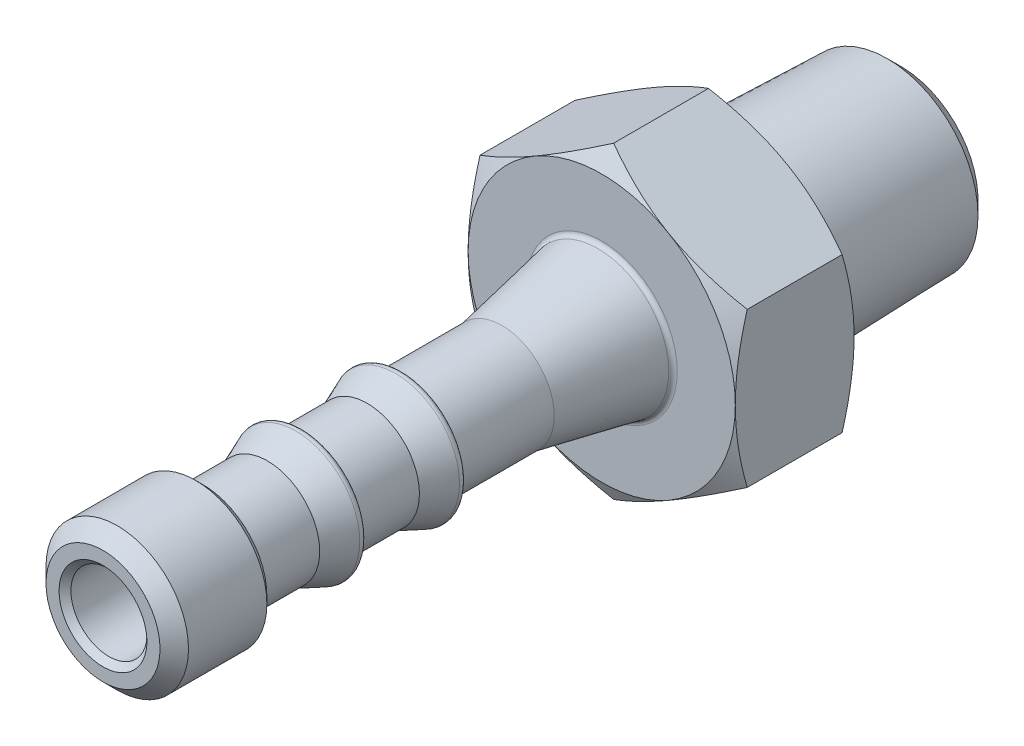
SolidWorks part; units mm, degrees
material "Alloy Steel"
ref_plane "Front Plane" through (0, 0, 0) normal (0, 0, 1) x (1, 0, 0)
ref_plane "Top Plane" through (0, 0, 0) normal (0, 1, 0) x (1, 0, 0)
ref_plane "Right Plane" through (0, 0, 0) normal (1, 0, 0) x (0, 0, -1)
sketch "Sketch1" plane through (0, 0, 0) normal (1, 0, 0) x (0, 0, -1)
  line L0 (-26.67, 0) -> (0, 0) construction
  line L1 (0, 0) -> (6.35, 0) construction
  line L2 (6.35, 0) -> (16.002, 0) construction
  line L3 (-26.67, 3.175) -> (-26.67, -3.175) construction
  line L5 (0, 7.1437) -> (0, -7.1437) construction
  line L6 (-26.67, 2.032) -> (-26.67, -2.032) construction
  line L7 (-26.67, 3.81) -> (-26.67, -3.81) construction
  line L8 (6.35, 7.1437) -> (6.35, -7.1437) construction
  line L9 (16.002, 3.175) -> (16.002, -3.175) construction
  line L10 (6.035, -5.1435) -> (6.035, 5.1435) construction
  line L11 (6.035, 5.1435) -> (16.002, 4.8332) construction
  line L12 (16.002, 4.8332) -> (16.002, -4.8332) construction
  line L13 (6.035, 5.1435) -> (6.9758, 5.1435) construction
  point P26 (6.035, 0)
sketch "Sketch2" plane through (0, 0, 0) normal (1, 0, 0) x (0, 0, -1)
  line L1 (-21.082, 2.794) -> (-17.8771, 2.794)
  line L2 (0, 4.0402) -> (0, 0)
  line L3 (0, 7.1437) -> (0, -7.1437) construction
  line L4 (-26.67, 0) -> (0, 0)
  line L7 (-26.67, 0) -> (-26.67, 3.81)
  line L9 (-26.67, 0) -> (0, 0) construction
  line L14 (-21.336, 3.048) -> (-21.336, 3.81)
  line L15 (-21.336, 3.81) -> (-26.67, 3.81)
  line L18 (-26.67, 7.1437) -> (-21.336, 7.1437) construction
  line L19 (-21.336, 7.1437) -> (-16.002, 7.1437) construction
  line L20 (-16.002, 7.1437) -> (-10.668, 7.1437) construction
  line L21 (-10.668, 7.1437) -> (-5.334, 7.1437) construction
  line L22 (-5.334, 7.1437) -> (0, 7.1437) construction
  line L23 (-26.67, 0) -> (-26.67, 7.1437) construction
  line L24 (-17.8771, 2.794) -> (-16.3512, 3.4105)
  line L25 (-16.002, 3.175) -> (-16.002, 3.048)
  line L26 (-15.748, 2.794) -> (-12.5431, 2.794)
  line L27 (-12.5431, 2.794) -> (-11.0172, 3.4105)
  line L28 (-10.668, 3.175) -> (-10.668, 3.048)
  line L29 (-10.414, 2.794) -> (-5.334, 2.794)
  line L30 (-5.334, 2.794) -> (-0.2055, 3.7909)
  line L38 (-16.256, 3.429) -> (-10.922, 3.429) construction
  arc A0 (-16.3512, 3.4105) -> (-16.002, 3.175) centre (-16.256, 3.175) cw
  arc A1 (-16.002, 3.048) -> (-15.748, 2.794) centre (-15.748, 3.048) ccw
  arc A2 (-11.0172, 3.4105) -> (-10.668, 3.175) centre (-10.922, 3.175) cw
  arc A3 (-10.668, 3.048) -> (-10.414, 2.794) centre (-10.414, 3.048) ccw
  arc A8 (-21.336, 3.048) -> (-21.082, 2.794) centre (-21.082, 3.048) ccw
  arc A10 (-0.2055, 3.7909) -> (0, 4.0402) centre (-0.254, 4.0402) ccw
  point P39 (-16.002, 2.794)
  point P44 (-10.668, 2.794)
  point P66 (-21.336, 2.794)
  dimension "D2" = 0.254
  dimension "D5" = 0.254
  dimension "D6" = 0.254
  dimension "D1" = 22
  dimension "D3" = 1.016
  dimension "D4" = 11
  dimension "D7" = 0.635
revolve "Revolve1" add sketch "Sketch2" angle 360 about L9
chamfer "Chamfer1" distance 0.381 angle 45 1 edges at (3.81, 0, 21.336)
chamfer "Chamfer2" distance 0.762 angle 45 1 edges at (3.81, 0, 26.67)
ref_plane "Plane1" through (0, 0, -16.002) normal (0, 0, 1) x (1, 0, 0)
sketch "Sketch3" plane through (0, 0, -16.002) normal (0, 0, 1) x (1, 0, 0)
  circle A0 centre (0, 0) radius 4.8332
extrude "Boss-Extrude1" add sketch "Sketch3" along normal up to vertex (9.652 mm away) draft 1.783 separate body up to point (0, 0, -6.35) draft outward yes
sketch "Sketch4" plane through (0, 0, -16.002) normal (0, 0, -1) x (-1, 0, 0)
  circle A1 centre (0, 0) radius 4.8332
  circle A2 centre (0, 0) radius 4.8332
  point P0 (0, 4.8332)
  dimension "D1" = 0
curve "Helix/Spiral1" [suppressed]
sketch "Sketch5" plane through (0, 0, 0) normal (1, 0, 0) x (0, 0, -1)
  line L0 (15.9432, 4.935) -> (16.8839, 4.935) construction
  line L1 (16.8839, 4.935) -> (16.4136, 4.1203) construction
  line L2 (16.4136, 4.1203) -> (15.9432, 4.935) construction
  line L3 (16.3548, 4.2221) -> (16.4724, 4.2221) construction
  line L4 (16.002, 4.8332) -> (16.8251, 4.8332) construction
  line L5 (16.4136, 4.1203) -> (16.4136, 4.2221) construction
  line L6 (16.4136, 4.8332) -> (16.4136, 4.935) construction
  line L7 (16.4136, 4.8841) -> (16.8545, 4.8841) construction
  line L8 (16.8545, 4.8841) -> (15.9432, 4.935)
  line L9 (15.9432, 4.935) -> (16.3548, 4.2221)
  line L10 (16.3548, 4.2221) -> (16.4724, 4.2221)
  line L11 (16.4724, 4.2221) -> (16.8545, 4.8841)
  line L12 (16.4136, 4.1203) -> (16.4136, -4.8204) construction
  line L13 (16.4136, -4.8204) -> (15.4733, -4.8496) construction
  line L14 (15.4733, -4.8496) -> (14.533, -4.8789) construction
  line L15 (14.533, -4.8789) -> (13.5927, -4.9082) construction
  line L16 (13.5927, -4.9082) -> (12.6524, -4.9375) construction
  line L17 (6.35, -5.1337) -> (16.002, -4.8332) construction
  dimension "D1" = 0.9407
  dimension "D2" = 0.1176
sweep "Cut-Sweep1" [suppressed] cut profiles "Sketch5" path "Helix/Spiral1"
sketch "Sketch6" plane through (0, 0, -16.002) normal (0, 0, -1) x (-1, 0, 0)
  circle A0 centre (0, 0) radius 4.1203
extrude "Cut-Extrude1" cut sketch "Sketch6" against normal up to vertex (9.652 mm away) draft 45 flip side to cut up to point (0, 0, -6.35)
sketch "Sketch7" plane through (0, 0, 0) normal (0, 0, -1) x (-1, 0, 0)
  line L1 (0, 8.2489) -> (-7.1437, 4.1244)
  line L2 (-7.1437, 4.1244) -> (-7.1437, -4.1244)
  line L3 (-7.1437, -4.1244) -> (0, -8.2489)
  line L4 (0, -8.2489) -> (7.1437, -4.1244)
  line L5 (7.1437, -4.1244) -> (7.1438, 4.1244)
  line L6 (7.1438, 4.1244) -> (0, 8.2489)
  circle A0 centre (0, 0) radius 7.1438 construction
extrude "Boss-Extrude2" add sketch "Sketch7" along normal up to vertex (6.35 mm away) up to point (0, 0, -6.35)
sketch "Sketch8" plane through (0, 0, 0) normal (0, 0, 1) x (1, 0, 0)
  circle A0 centre (0, 0) radius 7.1438 construction
  circle A1 centre (0, 0) radius 7.1438
extrude "Cut-Extrude2" cut sketch "Sketch8" against normal up to vertex (6.35 mm away) draft 60 flip side to cut up to point (0, 0, -6.35)
sketch "Sketch9" plane through (0, 0, -6.35) normal (0, 0, -1) x (-1, 0, 0)
  circle A1 centre (0, 0) radius 7.1438
  circle A2 centre (0, 0) radius 7.1438
  dimension "D1" = 0
extrude "Cut-Extrude3" cut sketch "Sketch9" against normal up to vertex (6.35 mm away) draft 60 flip side to cut up to point (0, 0, 0)
sketch "Sketch10" plane through (0, 0, 0) normal (1, 0, 0) x (0, 0, -1)
  line L0 (0, 0) -> (-26.67, 0) construction
  line L1 (-26.67, 2.032) -> (6.35, 2.032)
  line L2 (-26.67, 2.032) -> (-26.67, 0)
  line L3 (-26.67, 0) -> (6.35, 0)
  line L4 (6.35, 2.032) -> (6.35, 0)
revolve "Cut-Revolve1" cut sketch "Sketch10" angle 360 about L0
chamfer "Chamfer3" distance 0.3175 angle 45 1 edges at (-2.032, 0, 26.67)
sketch "Sketch11" plane through (0, 0, 0) normal (1, 0, 0) x (0, 0, -1)
  line L0 (0, 0) -> (16.002, 0) construction
  line L1 (0, 7.1437) -> (0, -7.1437) construction
  line L2 (16.002, 0) -> (16.002, 3.175)
  line L3 (16.002, 3.175) -> (6.35, 3.175)
  line L4 (6.35, 3.175) -> (4.4423, 0)
  line L5 (4.4423, 0) -> (16.002, 0)
  line L6 (6.35, 7.1437) -> (6.35, -7.1437) construction
  dimension "D1" = 59
revolve "Cut-Revolve2" cut sketch "Sketch11" angle 360 about L0
chamfer "Chamfer4" distance 0.508 angle 45 1 edges at (3.175, 0, -16.002)
equation "\"D3@Boss-Extrude1\" = \"Taper@Sketch1\""
equation "\"D6@Helix/Spiral1\" = \"Taper@Sketch1\""
equation "\"D4@Helix/Spiral1\" = \"Pitch@Sketch1\""
equation "\"D3@Helix/Spiral1\" = \"D4@Helix/Spiral1\" + \"L4@Sketch1\""
equation "\"D1@Sketch5\" = \"D4@Helix/Spiral1\""
equation "\"D2@Sketch5\" = \"D1@Sketch5\" / 8"
